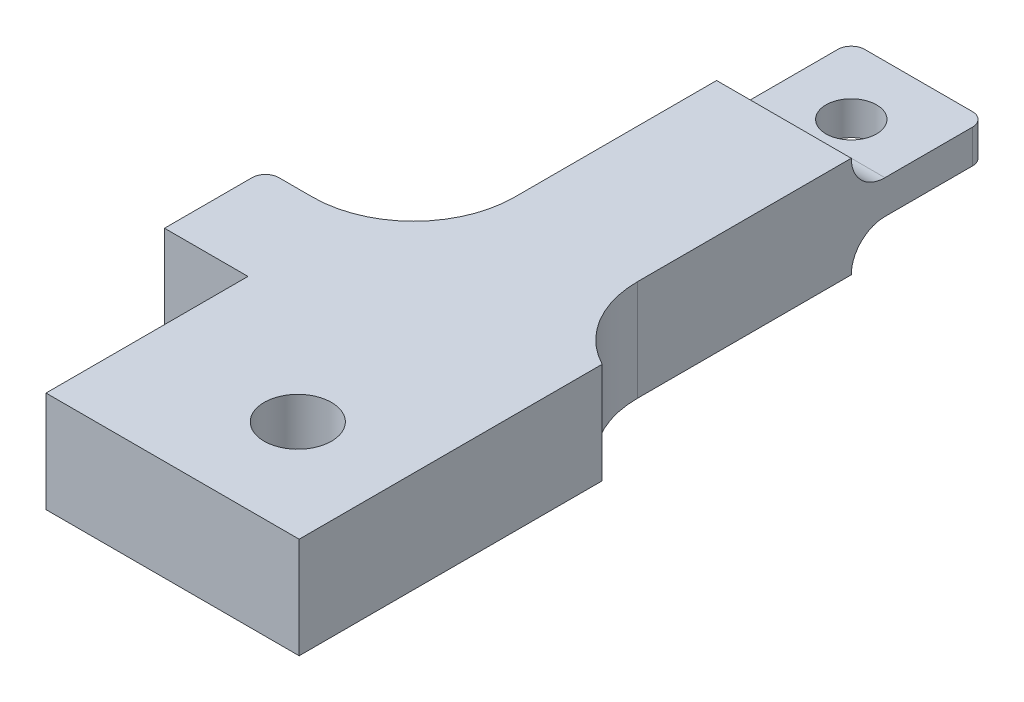
SolidWorks part; units mm, degrees
material "6061-T6 (SS)"
ref_plane "Front Plane" through (0, 0, 0) normal (0, 0, 1) x (1, 0, 0)
ref_plane "Top Plane" through (0, 0, 0) normal (0, 1, 0) x (1, 0, 0)
ref_plane "Right Plane" through (0, 0, 0) normal (1, 0, 0) x (0, 0, -1)
sketch "Sketch7" plane through (0, 0, 0) normal (0, 1, 0) x (1, 0, 0)
  line L0 (0, 0) -> (0, 19.05)
  line L1 (0, 19.05) -> (-7.874, 19.05)
  line L2 (-7.874, 19.05) -> (-7.874, 28.575)
  line L3 (23.876, 0) -> (23.876, 28.575)
  line L4 (23.876, 28.575) -> (18.796, 28.575)
  line L5 (-7.874, 28.575) -> (6.096, 28.575)
  line L6 (6.096, 28.575) -> (6.096, 69.85)
  line L7 (23.876, 0) -> (0, 0)
  line L10 (6.096, 69.85) -> (18.796, 69.85)
  line L11 (18.796, 28.575) -> (18.796, 69.85)
  dimension "D1" = 23.876
  dimension "D2" = 19.05
  dimension "D3" = 31.75
  dimension "D4" = 69.85
  dimension "D5" = 12.7
  dimension "D8" = 9.525
  dimension "D9" = 5.08
extrude "Stock" add sketch "Sketch7" along normal blind 9.525
sketch "Hole Pattern" plane through (0, 9.525, 0) normal (0, 1, 0) x (1, 0, 0)
  line L0 (0, 9.525) -> (23.876, 9.525) construction
  line L1 (0, 19.05) -> (0, 0) construction
  line L2 (18.796, 69.85) -> (6.096, 69.85) construction
  line L3 (6.096, 69.85) -> (6.096, 28.575) construction
  point P4 (12.446, 63.5)
  point P13 (14.224, 9.525)
  dimension "D1" = 14.224
  dimension "D2" = 6.35
  dimension "D3" = 6.35
hole_wizard "Mounting Hole" positions "Sketch11" profile "Sketch12" hole size "1/4" standard "ANSI Inch" end condition through all
sketch "Sketch11" plane through (0, 9.525, 0) normal (0, 1, 0) x (1, 0, 0)
  point P0 (14.224, 9.525)
sketch "Sketch12" plane through (14.224, 9.525, -9.525) normal (1, 0, 0) x (0, 0, 1)
  line L0 (0, 0) -> (0, 9.525)
  line L1 (0, 9.525) -> (3.175, 9.525)
  line L2 (3.175, 9.525) -> (3.175, 0)
  line L5 (3.175, 0) -> (0, 0)
  line L11 (0, -6.35) -> (0, 107.95) construction
  dimension "Thru Hole Dia." = 6.35
  dimension "Thru Hole Depth" = 9.525
hole_wizard "Spring Hole" positions "Sketch13" profile "Sketch14" hole size "3/16" standard "ANSI Inch" end condition through all
sketch "Sketch13" plane through (0, 9.525, 0) normal (0, 1, 0) x (1, 0, 0)
  point P0 (12.446, 63.5)
sketch "Sketch14" plane through (12.446, 9.525, -63.5) normal (1, 0, 0) x (0, 0, 1)
  line L0 (0, 0) -> (0, 9.525)
  line L1 (0, 9.525) -> (2.3812, 9.525)
  line L2 (2.3812, 9.525) -> (2.3812, 0)
  line L5 (2.3812, 0) -> (0, 0)
  line L11 (0, -6.35) -> (0, 107.95) construction
  dimension "Thru Hole Dia." = 4.7625
  dimension "Thru Hole Depth" = 9.525
fillet "Fillet3" radius 9.525 2 edges at (6.096, 4.7625, -28.575) (18.796, 4.7625, -28.575)
fillet "Fillet4" radius 1.27 3 edges at (-7.874, 4.7625, -28.575) (18.796, 4.7625, -69.85) (6.096, 4.7625, -69.85)
sketch "Sketch15" plane through (0, 9.525, 0) normal (0, 1, 0) x (1, 0, 0)
  line L0 (6.096, 68.58) -> (6.096, 38.1) construction
  line L1 (6.096, 69.85) -> (18.796, 69.85)
  line L2 (6.096, 69.85) -> (6.096, 57.15)
  line L3 (6.096, 57.15) -> (18.796, 57.15)
  line L4 (18.796, 69.85) -> (18.796, 57.15)
  line L5 (6.096, 69.85) -> (18.796, 57.15) construction
  line L6 (6.096, 57.15) -> (18.796, 69.85) construction
  line L7 (17.526, 69.85) -> (7.366, 69.85) construction
  line L8 (18.796, 36.9992) -> (18.796, 68.58) construction
  point P4 (12.446, 63.5)
  dimension "D1" = 12.7
extrude "Cut-Extrude1" cut sketch "Sketch15" against normal blind 3.175
sketch "Sketch16" plane through (0, 0, 0) normal (0, -1, 0) x (1, 0, 0)
  line L0 (18.796, -36.9992) -> (18.796, -68.58) construction
  line L1 (6.096, -69.85) -> (18.796, -69.85)
  line L2 (6.096, -69.85) -> (6.096, -57.15)
  line L3 (6.096, -57.15) -> (18.796, -57.15)
  line L4 (18.796, -69.85) -> (18.796, -57.15)
  line L5 (6.096, -69.85) -> (18.796, -57.15) construction
  line L6 (6.096, -57.15) -> (18.796, -69.85) construction
  line L7 (6.096, -68.58) -> (6.096, -38.1) construction
  line L8 (17.526, -69.85) -> (7.366, -69.85) construction
  line L9 (6.096, -57.15) -> (18.796, -57.15) construction
  point P4 (12.446, -63.5)
extrude "Cut-Extrude2" cut sketch "Sketch16" against normal blind 3.175
fillet "Fillet5" radius 3.175 2 edges at (12.446, 3.175, -57.15) (12.446, 6.35, -57.15)
